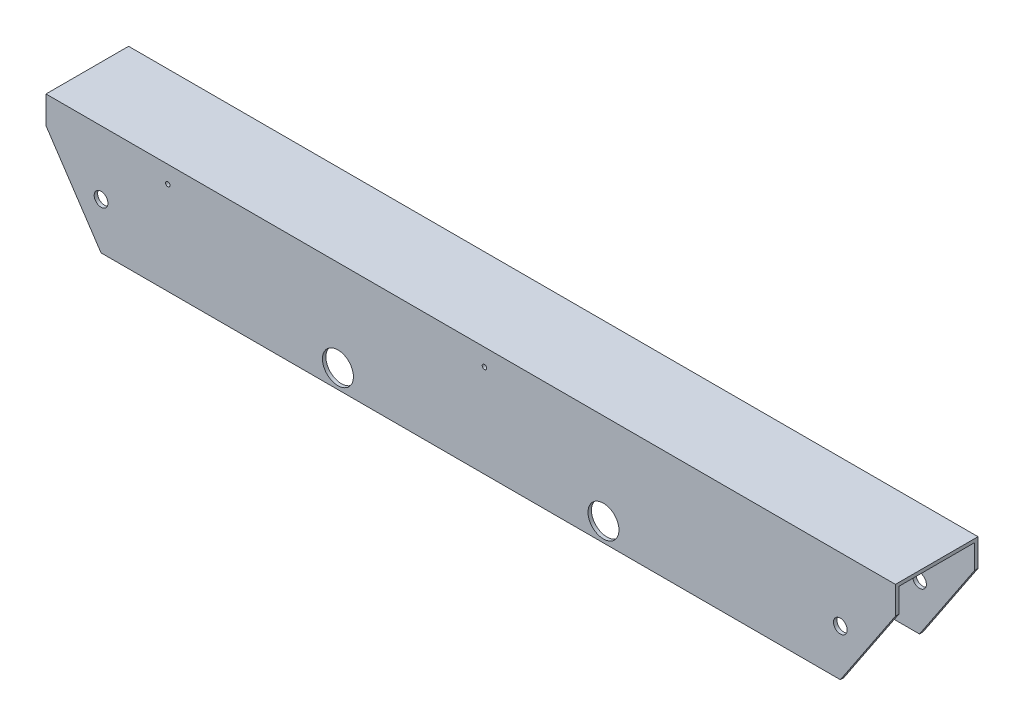
SolidWorks part; units mm, degrees
ref_plane "Front Plane" through (0, 0, 0) normal (0, 0, 1) x (1, 0, 0)
ref_plane "Top Plane" through (0, 0, 0) normal (0, 1, 0) x (1, 0, 0)
ref_plane "Right Plane" through (0, 0, 0) normal (1, 0, 0) x (0, 0, -1)
sketch "Sketch1" plane through (0, 0, 0) normal (1, 0, 0) x (0, 0, -1)
  line L0 (-34.925, 47.625) -> (-34.925, -47.625) construction
  line L1 (-38.1, 50.8) -> (38.1, 50.8)
  line L2 (-38.1, 50.8) -> (-38.1, -50.8)
  line L3 (-38.1, -50.8) -> (-34.925, -50.8)
  line L4 (38.1, 50.8) -> (38.1, -50.8)
  line L5 (-38.1, 50.8) -> (38.1, -50.8) construction
  line L6 (-38.1, -50.8) -> (38.1, 50.8) construction
  line L7 (34.925, 47.625) -> (34.925, -50.8)
  line L8 (-34.925, 47.625) -> (34.925, 47.625)
  line L9 (-34.925, 47.625) -> (-34.925, -50.8)
  line L10 (-34.925, -47.625) -> (34.925, -47.625) construction
  line L11 (34.925, 47.625) -> (34.925, -47.625) construction
  line L12 (-38.1, -50.8) -> (38.1, -50.8) construction
  line L13 (38.1, -50.8) -> (34.925, -50.8)
  point P0 (0, 0)
  dimension "D1" = 76.2
  dimension "D2" = 101.6
  dimension "D3" = 3.175
extrude "Boss-Extrude1" add sketch "Sketch1" along normal mid plane 783.7315
sketch "Sketch2" plane through (0, 0, 38.1) normal (0, 0, 1) x (1, 0, 0)
  line L1 (-391.8658, 50.8) -> (-391.8658, -50.8) construction
  line L8 (391.8658, -50.8) -> (-391.8658, -50.8) construction
  line L9 (0, -41.91) -> (0, 41.91) construction
  line L13 (0, 50.8) -> (0, -55.872) construction
  line L14 (391.8658, 50.8) -> (-391.8658, 50.8) construction
  circle A0 centre (-341.0658, -7.9375) radius 6.35
  circle A1 centre (122.5118, -33.3375) radius 14.2875
  circle A2 centre (341.0658, -7.9375) radius 6.35
  circle A4 centre (12.7, 34.925) radius 2.0828
  circle A5 centre (-279.4, 34.925) radius 2.0828
  circle A6 centre (-122.5118, -33.3375) radius 14.2875
  dimension "D1" = 122.5118
  dimension "D2" = 17.4625
  dimension "D3" = 220.025
  dimension "D4" = 218.5539
  dimension "D5" = 28.575
  dimension "D6" = 25.4
  dimension "D7" = 12.7
  dimension "D8" = 50.8
  dimension "D9" = 28.575
  dimension "D10" = 12.7
  dimension "D11" = 220.025
  dimension "D12" = 25.4
  dimension "D13" = 17.4625
  dimension "D22" = 15.875
  dimension "D23" = 15.875
  dimension "D24" = 112.4658
extrude "Cut-Extrude1" cut sketch "Sketch2" against normal blind 141.732
sketch "Sketch13" [suppressed] plane through (0, 0, 38.1) normal (0, 0, -1) x (-1, 0, 0)
  line L0 (-391.8658, -50.8) -> (391.8658, -50.8) construction
  line L2 (-25.4, 22.225) -> (0, 22.225)
  line L3 (-25.4, 22.225) -> (-25.4, 47.625)
  line L4 (-25.4, 47.625) -> (0, 47.625)
  line L5 (0, 22.225) -> (0, 47.625)
  line L6 (-25.4, 22.225) -> (0, 47.625) construction
  line L7 (-25.4, 47.625) -> (0, 22.225) construction
  line L8 (266.7, 22.225) -> (292.1, 22.225)
  line L9 (266.7, 22.225) -> (266.7, 47.625)
  line L10 (266.7, 47.625) -> (292.1, 47.625)
  line L11 (292.1, 22.225) -> (292.1, 47.625)
  line L12 (266.7, 22.225) -> (292.1, 47.625) construction
  line L13 (266.7, 47.625) -> (292.1, 22.225) construction
  circle A0 centre (-160.6118, -35.1235) radius 3.302
  circle A1 centre (-122.5118, -33.3375) radius 14.2875 construction
  circle A2 centre (-160.6118, 41.0765) radius 3.302
  circle A3 centre (-84.4118, 41.0765) radius 3.302
  circle A4 centre (-84.4118, -35.1235) radius 3.302
  point P12 (-12.7, 34.925)
  point P18 (279.4, 34.925)
  dimension "D1" = 6.604
  dimension "D2" = 15.6765
  dimension "D3" = 38.1
  dimension "D4" = 76.2
  dimension "D5" = 76.2
  dimension "D6" = 76.2
  dimension "D7" = 38.1
  dimension "D8" = 15.6765
  dimension "D9" = 25.4
  dimension "D10" = 25.4
  dimension "D11" = 25.4
  dimension "D12" = 25.4
extrude "Cut-Extrude11" [suppressed] cut sketch "Sketch13" along normal blind 33.2436
sketch "Sketch14" plane through (0, 0, -38.1) normal (0, 0, -1) x (-1, 0, 0)
  line L0 (-391.8658, -50.8) -> (391.8658, -50.8) construction
  line L2 (-25.4, 22.225) -> (0, 22.225)
  line L3 (-25.4, 22.225) -> (-25.4, 47.625)
  line L4 (-25.4, 47.625) -> (0, 47.625)
  line L5 (0, 22.225) -> (0, 47.625)
  line L6 (-25.4, 22.225) -> (0, 47.625) construction
  line L7 (-25.4, 47.625) -> (0, 22.225) construction
  line L8 (266.7, 22.225) -> (292.1, 22.225)
  line L9 (266.7, 22.225) -> (266.7, 47.625)
  line L10 (266.7, 47.625) -> (292.1, 47.625)
  line L11 (292.1, 22.225) -> (292.1, 47.625)
  line L12 (266.7, 22.225) -> (292.1, 47.625) construction
  line L13 (266.7, 47.625) -> (292.1, 22.225) construction
  circle A0 centre (-160.6118, -35.1235) radius 3.302
  circle A1 centre (-160.6118, 41.0765) radius 3.302
  circle A2 centre (-84.4118, 41.0765) radius 3.302
  circle A3 centre (-84.4118, -35.1235) radius 3.302
  circle A4 centre (-122.5118, -33.3375) radius 14.2875 construction
  point P12 (-12.7, 34.925)
  point P18 (279.4, 34.925)
  dimension "D1" = 6.604
  dimension "D2" = 15.6765
  dimension "D3" = 76.2
  dimension "D4" = 76.2
  dimension "D5" = 76.2
  dimension "D6" = 38.1
  dimension "D7" = 25.4
  dimension "D8" = 25.4
  dimension "D9" = 25.4
  dimension "D10" = 25.4
extrude "Cut-Extrude12" cut sketch "Sketch14" against normal blind 23.114
sketch "Sketch16" plane through (0, 0, 38.1) normal (0, 0, 1) x (1, 0, 0)
  line L1 (-391.8658, 50.8) -> (-391.8658, -50.8) construction
  line L2 (-391.8658, 25.4) -> (-341.0658, -50.8)
  line L3 (391.8658, -50.8) -> (-391.8658, -50.8) construction
  line L4 (-341.0658, -50.8) -> (-391.8658, -50.8)
  line L5 (-391.8658, -50.8) -> (-391.8658, 25.4)
  line L6 (0, 50.8) -> (0, -65.171) construction
  line L7 (0, -41.91) -> (0, 41.91) construction
  line L9 (341.0658, -50.8) -> (391.8658, -50.8)
  line L10 (391.8658, -50.8) -> (391.8658, 25.4)
  line L11 (391.8658, 25.4) -> (341.0658, -50.8)
  dimension "D1" = 91.581
  dimension "D2" = 76.2
  dimension "D4" = 50.8
extrude "Cut-Extrude13" cut sketch "Sketch16" against normal blind 101.6
